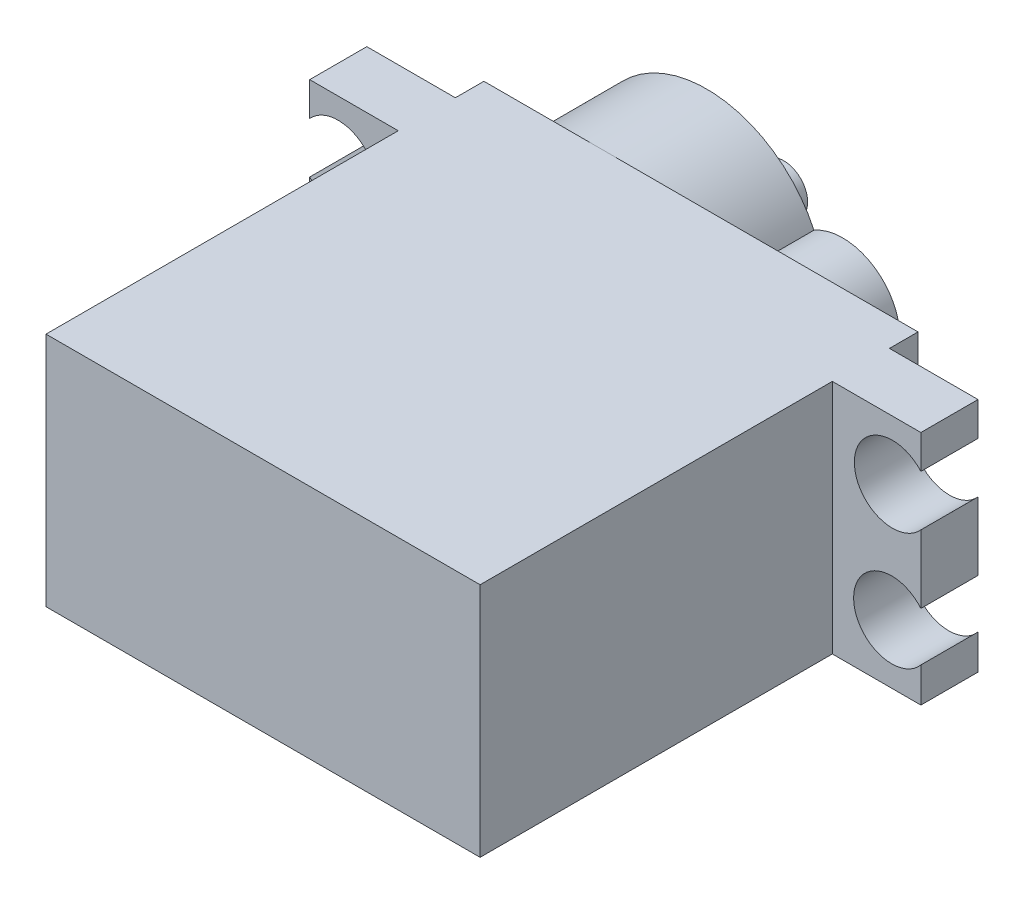
SolidWorks part; units mm, degrees
ref_plane "Front Plane" through (0, 0, 0) normal (0, 0, 1) x (1, 0, 0)
ref_plane "Top Plane" through (0, 0, 0) normal (0, 1, 0) x (1, 0, 0)
ref_plane "Right Plane" through (0, 0, 0) normal (1, 0, 0) x (0, 0, -1)
sketch "Sketch1" plane through (0, 0, 0) normal (0, 0, 1) x (1, 0, 0)
  line L0 (0, 0) -> (32.1, 0)
  line L1 (32.1, 0) -> (32.1, 12.4)
  line L2 (32.1, 12.4) -> (0, 12.4)
  line L3 (0, 12.4) -> (0, 0)
  line L4 (16.05, 12.4) -> (16.05, 0)
  line L5 (0, 12.4) -> (4.65, 12.4)
  line L6 (4.65, 12.4) -> (4.65, 0)
  line L7 (4.65, 0) -> (0, 0)
  line L8 (27.45, 12.4) -> (27.45, 0)
  line L9 (32.1, 12.4) -> (32.1, 0)
  point P6 (16.05, 6.2)
  point P10 (16.05, 12.4)
  dimension "D1" = 12.4
  dimension "D2" = 32.1
  dimension "D3" = 4.65
  dimension "D4" = 4.65
  dimension "D5" = 22.8
extrude "Boss-Extrude1" add sketch "Sketch1" along normal blind 18.5 contours L2 L6 L0 L4 | L8 L2 L4 L0 region at (10.35, 6.2, 0) region at (21.75, 6.2, 0)
extrude "Boss-Extrude2" add sketch "Sketch1<4>" against normal blind 2.5 separate body contours L6 L2 L3 L0 | L2 L8 L0 L1 region at (2.325, 6.2, 0) region at (29.775, 6.2, 0)
sketch "Sketch1<4>" plane through (0, 0, 0) normal (0, 0, 1) x (1, 0, 0) same geometry as "Sketch1"
extrude "Boss-Extrude8" add sketch "Sketch1<11>" against normal blind 3 contours L2 L8 L0 L1 | L6 L2 L3 L0 region at (2.325, 6.2, 0) region at (29.775, 6.2, 0)
sketch "Sketch1<11>" plane through (0, 0, 0) normal (0, 0, 1) x (1, 0, 0) same geometry as "Sketch1"
extrude "Boss-Extrude9" add sketch "Sketch1<13>" against normal blind 4.5 contours L8 L2 L4 L0 | L2 L6 L0 L4 region at (10.35, 6.2, 0) region at (21.75, 6.2, 0)
sketch "Sketch1<13>" plane through (0, 0, 0) normal (0, 0, 1) x (1, 0, 0) same geometry as "Sketch1"
sketch "Sketch8" plane through (0, 0, -4.5) normal (0, 0, -1) x (-1, 0, 0)
  arc A0 (-16.4823, 3.6081) -> (-16.4823, 8.7919) centre (-10.85, 6.2) ccw
  arc A1 (-16.4823, 8.7919) -> (-16.4823, 3.6081) centre (-17.993, 6.2) ccw
extrude "Boss-Extrude11" add sketch "Sketch8" along normal blind 5.5
sketch "Sketch10" plane through (0, 0, -10) normal (0, 0, -1) x (-1, 0, 0)
  circle A0 centre (-10.9028, 5.9103) radius 1.25
extrude "Boss-Extrude12" add sketch "Sketch10" along normal blind 4
extrude "Boss-Extrude13" add sketch "Sketch8<2>" along normal blind 5
sketch "Sketch8<2>" plane through (0, 0, -4.5) normal (0, 0, -1) x (-1, 0, 0) same geometry as "Sketch8"
sketch "Sketch15" plane through (0, 0, -3) normal (0, 0, -1) x (-1, 0, 0)
  line L1 (-32.1, 0) -> (-32.1, 12.4) construction
  line L2 (0, 12.4) -> (0, 0) construction
  line L3 (-32.1, 6.2) -> (-32.1, 0)
  line L5 (0, 0) -> (0, 6.2)
  circle A0 centre (-30.5672, 3.1115) radius 2
  circle A1 centre (-30.6057, 9.3) radius 2
  circle A2 centre (-1.4943, 3.1) radius 2
  circle A3 centre (-1.4943, 9.3) radius 2
  line M12 (-32.1, 12.4) -> (-32.1, 0)
extrude "Cut-Extrude1" cut sketch "Sketch15" against normal up to next contours A1 M12 | A3 | A2 L5 | A0 region at (30.4712, 9.3, -3) region at (1.6288, 3.1, -3) region at (1.4943, 9.3, -3)
